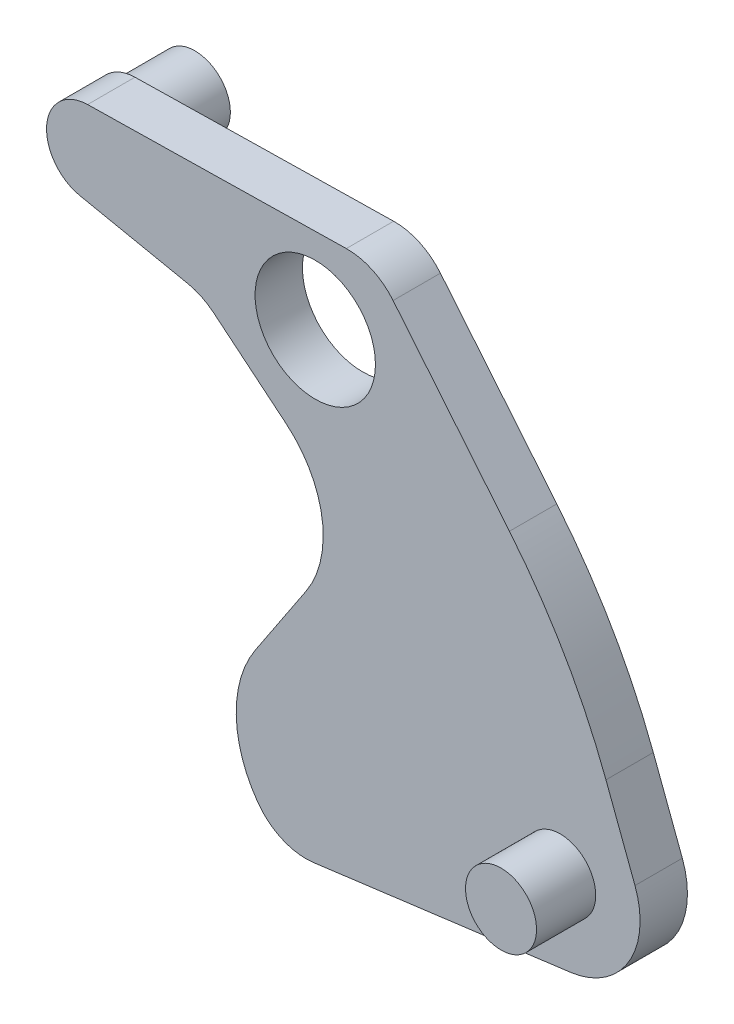
SolidWorks part; units mm, degrees
ref_plane "Alzado" through (0, 0, 0) normal (0, 0, 1) x (1, 0, 0)
ref_plane "Planta" through (0, 0, 0) normal (0, 1, 0) x (1, 0, 0)
ref_plane "Vista lateral" through (0, 0, 0) normal (1, 0, 0) x (0, 0, -1)
ref_plane "Plane1" through (0, 0, 0) normal (0, 0, -1) x (-1, 0, 0)
sketch "Sketch1" plane through (0, 0, 0) normal (0, 0, -1) x (-1, 0, 0)
  line L0 (1.9236, 0.6862) -> (-0.5042, 0.7295)
  line L1 (-0.5042, 0.7295) -> (-2.1652, -1.2925)
  line L2 (-2.1652, -1.2925) -> (-3.002, -3.514)
  line L3 (-3.002, -3.514) -> (0.2445, -3.9363)
  line L4 (0.5055, -2.5958) -> (-0.3529, -1.3038)
  line L5 (-0.3529, -1.3038) -> (0.9555, -0.2255)
  line L6 (0.9555, -0.2255) -> (1.9884, -0.0134)
  arc A0 (0.2445, -3.9363) -> (0.5055, -2.5958) centre (-0.3043, -3.1338) ccw
  arc A1 (1.9884, -0.0134) -> (1.9236, 0.6862) centre (1.9173, 0.3328) ccw
  dimension "D1" = 0.9722
  dimension "D2" = 0.3534
  dimension "D3" = 0.0648
  dimension "D4" = 0.0711
  dimension "D5" = 1.0328
  dimension "D6" = 1.4829
  dimension "D7" = 1.7439
  dimension "D8" = 2.2927
  dimension "D9" = 2.3413
  dimension "D10" = 2.4925
  dimension "D11" = 4.1535
  dimension "D12" = 4.9904
  dimension "D13" = 2.022
  dimension "D14" = 2.0333
  dimension "D17" = 4.2434
extrude "Boss-Extrude1" add sketch "Sketch1" against normal blind 0.4
ref_plane "Plane2" through (0, -2.9544, 0) normal (0, -1, 0) x (1, 0, 0)
sketch "Sketch2" plane through (0, -2.9544, 0) normal (0, -1, 0) x (1, 0, 0)
  line L0 (2.3698, 0.9) -> (2.0698, 0.9)
  line L1 (2.0698, 0.9) -> (2.0698, 0.4)
  line L2 (2.0698, 0.4) -> (2.3698, 0.4)
  line L3 (2.3698, 0.4) -> (2.3698, 0.9)
  line L4 (2.0698, 0.9) -> (2.0698, 0.4) construction
  dimension "D1" = 0.3
  dimension "D2" = 0.5
revolve "Revolve1" add sketch "Sketch2" angle 360 about L4 reverse direction yes
ref_plane "Plane3" through (0, 0.3328, 0) normal (0, 1, 0) x (1, 0, 0)
sketch "Sketch3" plane through (0, 0.3328, 0) normal (0, 1, 0) x (1, 0, 0)
  line L0 (-1.6173, 0.5) -> (-1.9173, 0.5)
  line L1 (-1.9173, 0.5) -> (-1.9173, 0)
  line L2 (-1.9173, 0) -> (-1.6173, 0)
  line L3 (-1.6173, 0) -> (-1.6173, 0.5)
  line L4 (-1.9173, 0.5) -> (-1.9173, 0) construction
  dimension "D1" = 0.3
  dimension "D2" = 0.5
revolve "Revolve2" add sketch "Sketch3" angle 360 about L4 reverse direction yes
hole_wizard "Hole1" positions "Sketch5" profile "Sketch4" legacy
sketch "Sketch5" plane through (0, 0, 0.4) normal (0, 0, 1) x (1, 0, 0)
  point P0 (0, 0)
sketch "Sketch4" plane through (0, 0, 0.4) normal (1, 0, 0) x (0, -1, 0)
  line L0 (0, 0) -> (0, 0.9)
  line L1 (0, 0.9) -> (0.5085, 0.9)
  line L2 (0.5085, 0.9) -> (0.5085, 0)
  line L3 (0.5085, 0) -> (0, 0)
  line L4 (0, 110) -> (0, -10) construction
  dimension "Diameter" = 1.017
  dimension "Depth" = 0.9
fillet "Fillet1" radius 0.5 3 edges at (0.5042, 0.7295, 0.2) (-0.2445, -3.9363, 0.2) (-0.9555, -0.2255, 0.2) tangent propagation no
fillet "Fillet2" radius 0.6751 1 edges at (3.002, -3.514, 0.2) tangent propagation no
fillet "Fillet3" radius 0.861 1 edges at (0.3529, -1.3038, 0.2) tangent propagation no
fillet "Fillet4" radius 5 1 edges at (2.1652, -1.2925, 0.2) tangent propagation no
ref_axis "Axis1" through (-1.9173, 0.3328, -0.5) along (0, 0, 1)
ref_axis "Axis2" through (2.0698, -2.9544, 0.9) along (0, 0, -1)
